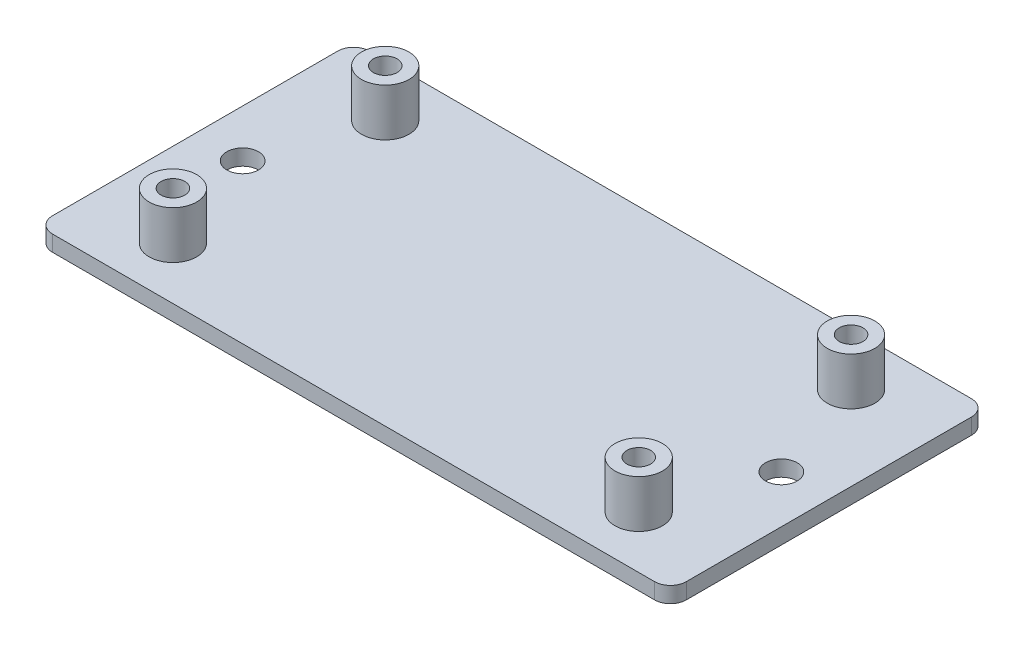
SolidWorks part; units mm, degrees
ref_plane "Спереди" through (0, 0, 0) normal (0, 0, 1) x (1, 0, 0)
ref_plane "Сверху" through (0, 0, 0) normal (0, 1, 0) x (1, 0, 0)
ref_plane "Справа" through (0, 0, 0) normal (1, 0, 0) x (0, 0, -1)
sketch "Эскиз1" plane through (0, 0, 0) normal (0, 1, 0) x (1, 0, 0)
  line L1 (0, 0) -> (80, 0)
  line L2 (0, 0) -> (0, -40)
  line L3 (0, -40) -> (80, -40)
  line L4 (80, 0) -> (80, -40)
  dimension "D1" = 40
  dimension "D2" = 80
extrude "Бобышка-Вытянуть1" add sketch "Эскиз1" along normal blind 2
sketch "Эскиз2" plane through (0, 2, 0) normal (0, 1, 0) x (1, 0, 0)
  line L0 (0, 0) -> (0, -40) construction
  line L1 (80, 0) -> (0, 0) construction
  line L2 (0, -40) -> (80, -40) construction
  line L3 (80, -40) -> (80, 0) construction
  circle A0 centre (10.6, -6.6) radius 3
  circle A1 centre (10.6, -33.4) radius 3
  circle A2 centre (69.4, -6.6) radius 3
  circle A3 centre (69.4, -33.4) radius 3
  dimension "D1" = 10.6
  dimension "D2" = 6.6
  dimension "D3" = 10.6
  dimension "D4" = 6.6
  dimension "D5" = 6.6
  dimension "D6" = 10.6
  dimension "D7" = 10.6
  dimension "D8" = 6.6
  dimension "D9" = 6
  dimension "D10" = 6
  dimension "D11" = 6
  dimension "D12" = 6
extrude "Бобышка-Вытянуть2" add sketch "Эскиз2" along normal blind 6
sketch "Эскиз3" plane through (0, 8, 0) normal (0, 1, 0) x (1, 0, 0)
  circle A0 centre (10.6, -6.6) radius 1.5
  circle A1 centre (10.6, -33.4) radius 1.5
  circle A2 centre (69.4, -6.6) radius 1.5
  circle A3 centre (69.4, -33.4) radius 1.5
  dimension "D1" = 3
  dimension "D2" = 3
  dimension "D3" = 3
  dimension "D4" = 3
extrude "Вырез-Вытянуть1" cut sketch "Эскиз3" against normal through all both and the other way through all
sketch "Эскиз4" plane through (0, 2, 0) normal (0, 1, 0) x (1, 0, 0)
  line L0 (0, -20) -> (80, -20) construction
  line L1 (0, 0) -> (0, -40) construction
  line L2 (80, -40) -> (80, 0) construction
  circle A0 centre (6, -20) radius 2
  circle A1 centre (74, -20) radius 2
  dimension "D1" = 6
  dimension "D2" = 4
  dimension "D3" = 6
  dimension "D4" = 4
extrude "Вырез-Вытянуть2" cut sketch "Эскиз4" against normal through all both and the other way through all
fillet "Скругление1" radius 2 1 edges at (0, 1, 0) type face fillet first side face at (40, 1, 0) second side face at (0, 1, 20)
fillet "Скругление2" radius 2 1 edges at (0, 1, 40) type face fillet first side face at (0, 1, 21) second side face at (40, 1, 40)
fillet "Скругление3" radius 2 1 edges at (80, 1, 40) type face fillet first side face at (41, 1, 40) second side face at (80, 1, 20)
fillet "Скругление4" radius 2 1 edges at (80, 1, 0) type face fillet first side face at (41, 1, 0) second side face at (80, 1, 19)
